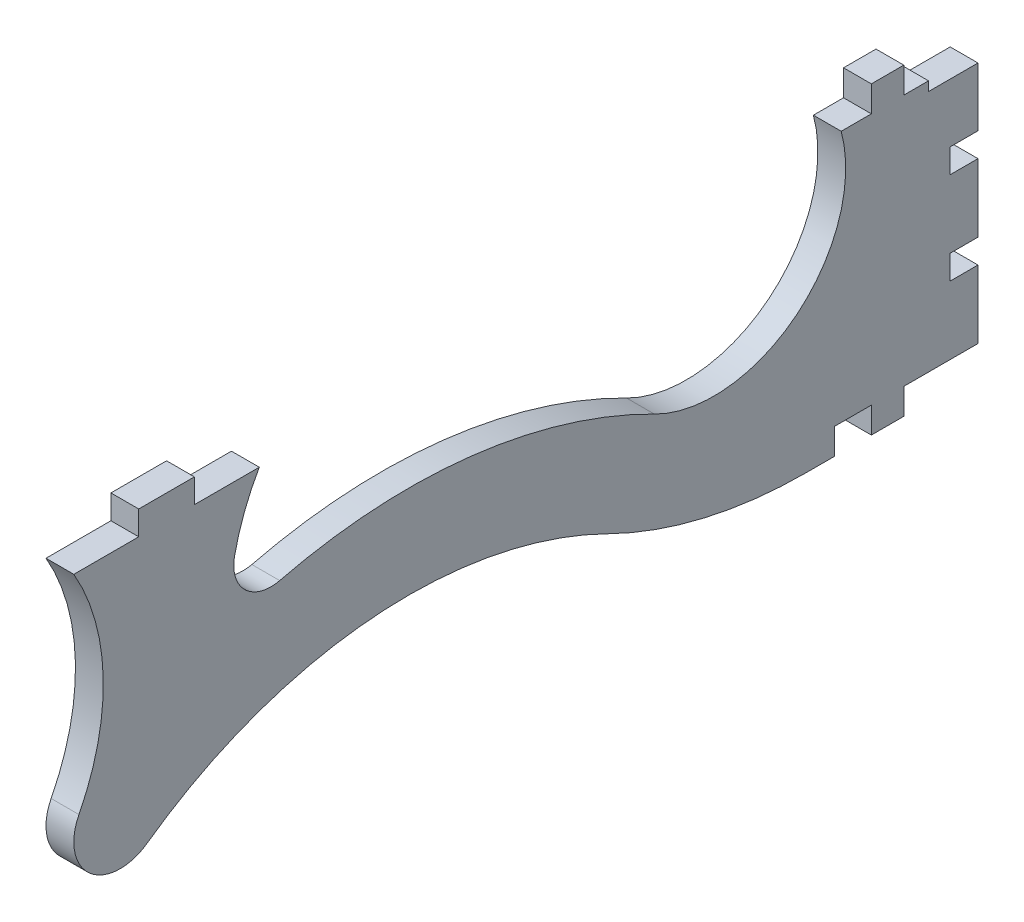
SolidWorks part; units mm, degrees
ref_plane "Front Plane" through (0, 0, 0) normal (0, 0, 1) x (1, 0, 0)
ref_plane "Top Plane" through (0, 0, 0) normal (0, 1, 0) x (1, 0, 0)
ref_plane "Right Plane" through (0, 0, 0) normal (1, 0, 0) x (0, 0, -1)
sketch "Sketch1" plane through (0, 0, 0) normal (1, 0, 0) x (0, 0, -1)
  line L0 (-80, 30) -> (-87, 30)
  line L1 (-87, 30) -> (-87, 32.6)
  line L2 (-87, 32.6) -> (-93, 32.6)
  line L3 (-93, 32.6) -> (-93, 30)
  line L4 (-93, 30) -> (-100, 30)
  line L19 (55, 0) -> (-55, 0) construction
  line L20 (0, -1000) -> (0, 49000) construction
  line L21 (-1.5, 18.6204) -> (-1.5, 0) construction
  line L22 (55, 30) -> (-55, 30) construction
  line L23 (-95, 0) -> (0, 0) construction
  line L24 (-100, 30) -> (-100, 5) construction
  line L25 (-18, 0) -> (-21, 0)
  line L26 (-100, 30) -> (-82.6795, 0) construction
  line L27 (-18, 0) -> (-18, 2.8)
  line L28 (-18, 2.8) -> (-14, 2.8)
  line L29 (-14, 2.8) -> (-14, 0)
  line L30 (-14, 0) -> (-10.5, 0)
  line L31 (-10.5, 0) -> (-10.5, 2.8)
  line L32 (-10.5, 2.8) -> (-2.5, 2.8)
  line L33 (-2.5, 2.8) -> (-2.5, 10.1333)
  line L34 (-2.5, 10.1333) -> (-5.5, 10.1333)
  line L35 (-5.5, 10.1333) -> (-5.5, 12.7333)
  line L36 (-5.5, 12.7333) -> (-2.5, 12.7333)
  line L37 (-2.5, 12.7333) -> (-2.5, 20.0667)
  line L38 (-2.5, 20.0667) -> (-5.5, 20.0667)
  line L39 (-5.5, 20.0667) -> (-5.5, 22.6667)
  line L40 (-5.5, 22.6667) -> (-2.5, 22.6667)
  line L41 (-2.5, 22.6667) -> (-2.5, 30)
  line L42 (-2.5, 30) -> (-10.5, 30)
  line L43 (-10.5, 30) -> (-10.5, 32.8)
  line L44 (-10.5, 32.8) -> (-14, 32.8)
  line L45 (-14, 32.8) -> (-14, 30)
  line L46 (-14, 30) -> (-17.2497, 30)
  line L47 (-80, 30) -> (-97.3205, 0) construction
  line L48 (-17.2497, 30) -> (-9.2113, 0) construction
  line L49 (-37.4002, 13.662) -> (-42.4358, 5) construction
  line L50 (-63.8715, 20) -> (-63.8715, 10) construction
  line L51 (-63.8715, 10) -> (-63.8715, 0) construction
  arc A0 (-100, 30) -> (-99.4467, 7.2862) centre (-120.5494, 18.1358) cw
  arc A1 (-99.4467, 7.2862) -> (-92.088, 0.9355) centre (-95, 5) ccw
  arc A2 (-92.088, 0.9355) -> (-42.4358, 5) centre (-63.8715, -38.4492) cw
  arc A3 (-42.4358, 5) -> (-21, 0) centre (-21, 48.4492) ccw
  arc A4 (-80, 30) -> (-82.67, 23.0244) centre (-59.4506, 18.1358) ccw
  arc A7 (-82.67, 23.0244) -> (-77.8024, 18.3156) centre (-78.7558, 22.2003) ccw
  arc A8 (-77.8024, 18.3156) -> (-37.4002, 13.662) centre (-63.8715, -38.4492) cw
  arc A9 (-17.2497, 30) -> (-37.4002, 13.662) centre (-30.968, 26.3242) cw
  point P18 (-5.5, 11.4333)
  point P35 (-90, 32.6)
  point P52 (-5.5, 21.3667)
  point P53 (-2.5, 16.4)
  point P58 (-18, 32.8)
  dimension "D7" = 5
  dimension "D16" = 4
  dimension "D18" = 10
  dimension "D1" = 4
  dimension "D2" = 1.5
  dimension "D3" = 2.8
  dimension "D4" = 2.6
  dimension "D5" = 6
  dimension "D6" = 2.6
  dimension "D8" = 3
  dimension "D9" = 30
  dimension "D10" = 3.5
  dimension "D11" = 1
  dimension "D12" = 3
  dimension "D15" = 60
  dimension "D17" = 15
  dimension "D19" = 5
extrude "Boss-Extrude1" add sketch "Sketch1" along normal blind 1.5 and the other way blind 1.5
sketch "Sketch2" plane through (1.5, 0, 0) normal (1, 0, 0) x (0, 0, -1)
  line L0 (-10.5, 30) -> (-7.8333, 30) construction
  line L1 (-7.8333, 30) -> (-5.1667, 30)
  line L2 (-5.1667, 30) -> (-2.5, 30)
  line L3 (-7.8333, 30) -> (-7.8333, 29)
  line L4 (-7.8333, 29) -> (-2.5, 29)
  line L5 (-2.5, 29) -> (-2.5, 30)
  dimension "D1" = 1
extrude "Cut-Extrude1" cut sketch "Sketch2" against normal through all
